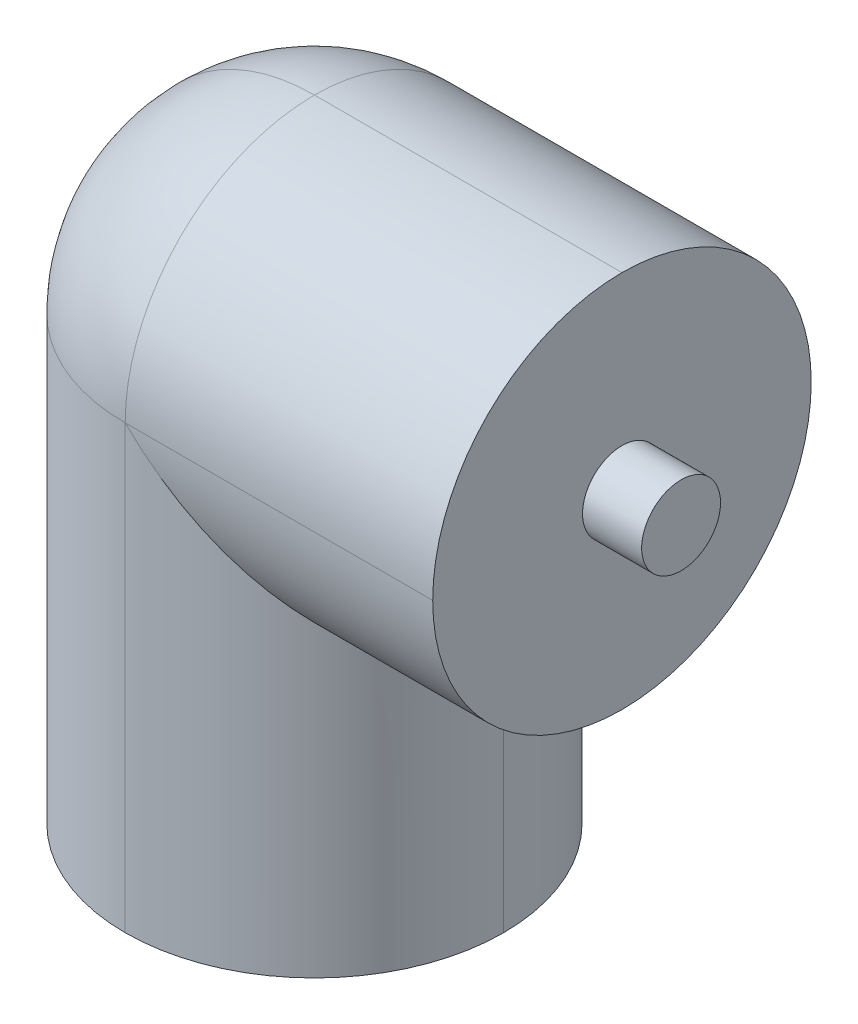
SolidWorks part; units mm, degrees
ref_plane "Front Plane" through (0, 0, 0) normal (0, 0, 1) x (1, 0, 0)
ref_plane "Top Plane" through (0, 0, 0) normal (0, 1, 0) x (1, 0, 0)
ref_plane "Right Plane" through (0, 0, 0) normal (1, 0, 0) x (0, 0, -1)
sketch "Sketch1" plane through (0, 0, 0) normal (0, 1, 0) x (1, 0, 0)
  line L1 (0, 0) -> (48, 0)
  line L2 (0, 0) -> (0, 48)
  line L3 (0, 48) -> (48, 48)
  line L4 (48, 0) -> (48, 48)
  dimension "D1" = 48
  dimension "D2" = 48
extrude "Boss-Extrude1" add sketch "Sketch1" along normal blind 80
sketch "Sketch2" plane through (48, 0, 0) normal (1, 0, 0) x (0, 0, -1)
  line L0 (48, 80) -> (48, 0) construction
  line L1 (0, 80) -> (48, 80)
  line L2 (0, 80) -> (0, 32)
  line L3 (0, 32) -> (48, 32)
  line L4 (48, 80) -> (48, 32)
  dimension "D1" = 48
extrude "Boss-Extrude2" add sketch "Sketch2" along normal blind 15
fillet "Fillet2" radius 24 8 edges at (48, 16, 0) (55.5, 32, 0) (55.5, 32, -48) (48, 16, -48) (0, 40, -48) (0, 40, 0) (31.5, 80, -48) (31.5, 80, 0)
sketch "Sketch3" plane through (0, 0, 0) normal (0, -1, 0) x (-1, 0, 0)
  circle A0 centre (-24, 24) radius 5
  dimension "D1" = 10
extrude "Boss-Extrude3" add sketch "Sketch3" along normal mid plane 15
sketch "Sketch4" plane through (63, 0, 0) normal (1, 0, 0) x (0, 0, -1)
  circle A0 centre (24, 56) radius 5
  dimension "D1" = 10
extrude "Boss-Extrude4" add sketch "Sketch4" along normal mid plane 15
